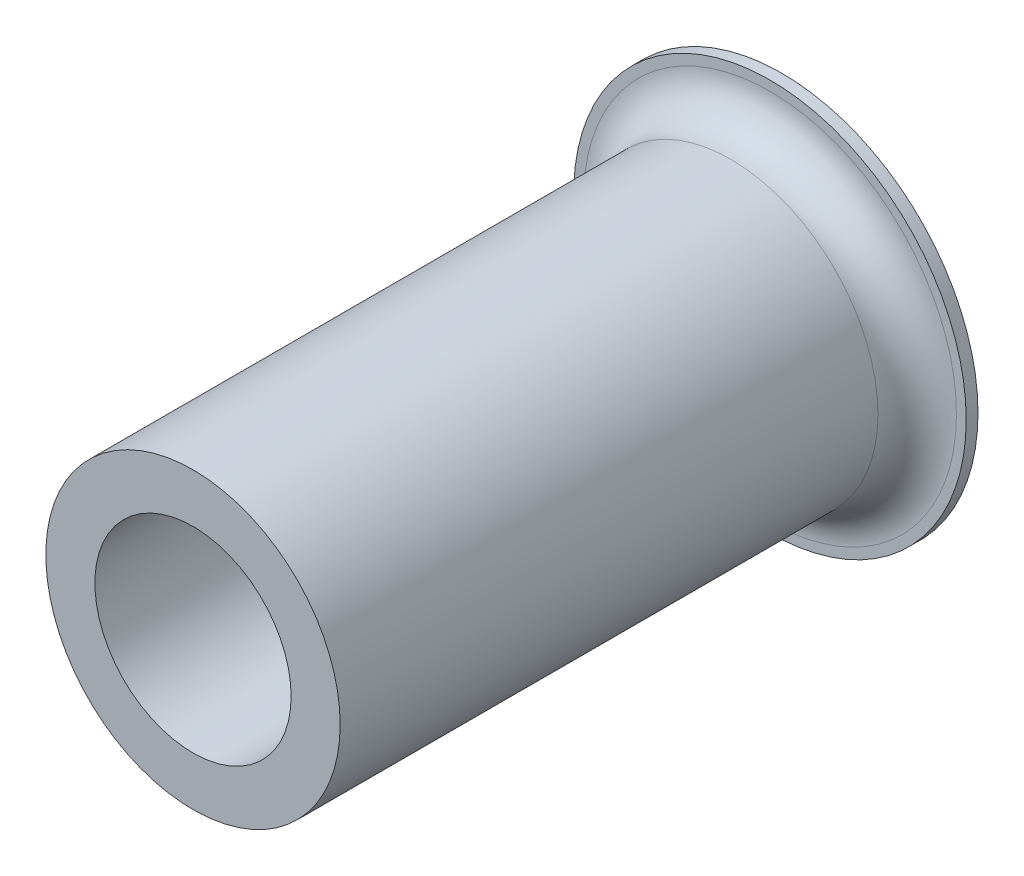
SolidWorks part; units mm, degrees
ref_plane "xy_plane" through (0, 0, 0) normal (0, 0, 1) x (1, 0, 0)
ref_plane "zx_plane" through (0, 0, 0) normal (0, 1, 0) x (1, 0, 0)
ref_plane "yz_plane" through (0, 0, 0) normal (1, 0, 0) x (0, 0, -1)
ref_plane "xMid_plane" through (0, 0, 0) normal (1, 0, 0) x (0, 0, -1)
ref_plane "xMin_plane" through (-0.6173, 0, 0) normal (1, 0, 0) x (0, 0, -1)
ref_plane "xMax_plane" through (0.6173, 0, 0) normal (1, 0, 0) x (0, 0, -1)
ref_plane "yMid_plane" through (0, 0, 0) normal (0, 1, 0) x (1, 0, 0)
ref_plane "yMin_plane" through (0, -0.6173, 0) normal (0, 1, 0) x (1, 0, 0)
ref_plane "yMax_plane" through (0, 0.6173, 0) normal (0, 1, 0) x (1, 0, 0)
ref_plane "zMid_plane" through (0, 0, 0) normal (0, 0, 1) x (1, 0, 0)
ref_plane "zMin_plane" through (0, 0, -0.6173) normal (0, 0, 1) x (1, 0, 0)
ref_plane "zMax_plane" through (0, 0, 0.6173) normal (0, 0, 1) x (1, 0, 0)
ref_axis "x_axis" through (-80.9, 0, 0) along (1, 0, 0)
ref_axis "y_axis" through (0, -50, 0) along (0, 1, 0)
ref_axis "z_axis" through (0, 0, -80.9) along (0, 0, 1)
sketch "Sketch1" plane through (0, 0, 0) normal (0, 0, 1) x (1, 0, 0)
  circle A0 centre (0, 0) radius 37.5
  dimension "D1" = 75
extrude "Boss-Extrude1" add sketch "Sketch1" along normal blind 150
sketch "Sketch2" plane through (0, 0, 0) normal (0, 0, 1) x (1, 0, 0)
  circle A0 centre (0, 0) radius 25
  dimension "D1" = 50
extrude "Cut-Extrude1" cut sketch "Sketch2" against normal offset from surface (145 mm away) 5 from surface up to face at (37.5, 0, 0) starting at face at (37.5, 0, 150)
sketch "Sketch3" plane through (0, 0, 0) normal (0, 0, 1) x (1, 0, 0)
  circle A0 centre (0, 0) radius 50
  dimension "D1" = 100
extrude "Boss-Extrude2" add sketch "Sketch3" along normal blind 3
fillet "Fillet1" radius 10 1 edges at (37.5, 0, 3)
equation "\"D1@xMin_plane\"=\"externalParameters.this.extentX\"/2"
equation "\"D1@xMax_plane\"=\"externalParameters.this.extentX\"/2"
equation "\"D1@yMin_plane\"=\"externalParameters.this.extentY\"/2"
equation "\"D1@yMax_plane\"=\"externalParameters.this.extentY\"/2"
equation "\"D1@zMin_plane\"=\"externalParameters.this.extentZ\"/2"
equation "\"D1@zMax_plane\"=\"externalParameters.this.extentZ\"/2"
